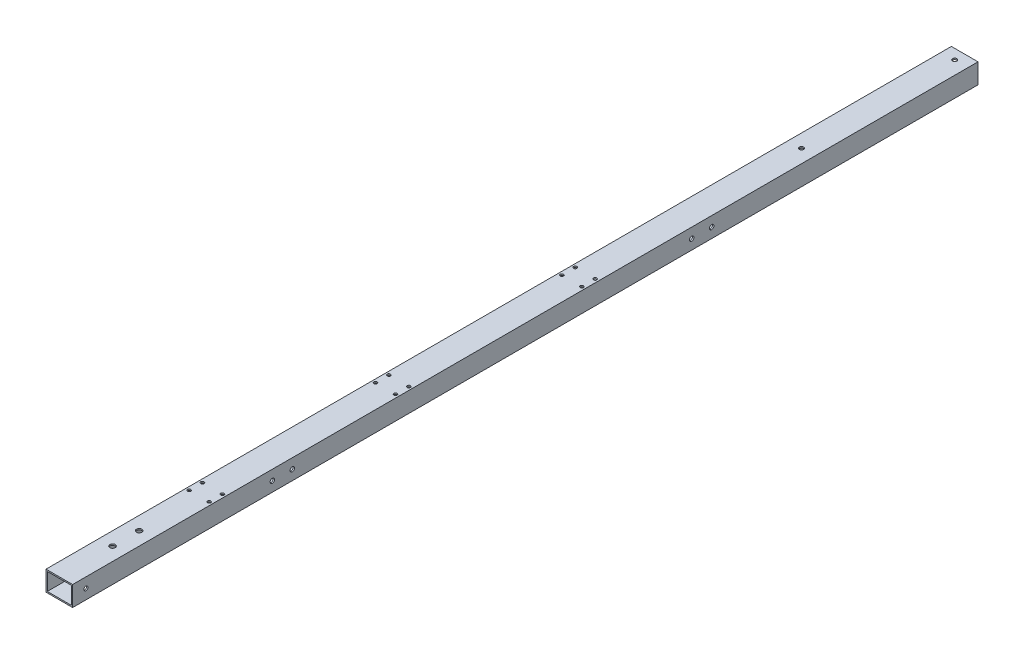
SolidWorks part; units mm, degrees
material "1060 合金"
ref_plane "前视基准面" through (0, 0, 0) normal (0, 0, 1) x (1, 0, 0)
ref_plane "上视基准面" through (0, 0, 0) normal (0, 1, 0) x (1, 0, 0)
ref_plane "右视基准面" through (0, 0, 0) normal (1, 0, 0) x (0, 0, -1)
other "Configuration Table"
sketch "草图1" plane through (0, 0, 0) normal (0, 0, 1) x (1, 0, 0)
  line L1 (0, 0) -> (20, 0)
  line L2 (0, 0) -> (0, -15)
  line L3 (0, -15) -> (20, -15)
  line L4 (20, 0) -> (20, -15)
  dimension "D1" = 15
  dimension "D2" = 20
extrude "拉伸-薄壁1" add sketch "草图1" along normal blind 800 thin thin type one direction reverse wall 1
sketch "草图2" plane through (0, -15, 0) normal (0, -1, 0) x (1, 0, 0)
  circle A1 centre (7.5, 825) radius 2.6
  circle A2 centre (7.5, 825) radius 2.6
  dimension "D1" = 0
extrude "切除-拉伸1" [suppressed] cut sketch "草图2" against normal up to next
sketch "草图3" plane through (0, 0, 0) normal (-1, 0, 0) x (0, 0, 1)
  line L0 (800, 0) -> (0, 0) construction
  line L1 (0, 0) -> (0, -15) construction
  circle A0 centre (215, -7.5) radius 1.7
  circle A1 centre (170, -7.5) radius 1.7
  dimension "D1" = 3.4
  dimension "D2" = 3.4
  dimension "D3" = 45
  dimension "D4" = 7.5
  dimension "D5" = 7.5
  dimension "D6" = 170
sketch "草图4" plane through (20, 0, 0) normal (1, 0, 0) x (0, 0, -1)
  line L0 (-800, -15) -> (0, -15) construction
  line L1 (-800, -15) -> (-800, 0) construction
  circle A0 centre (-790, -7.5) radius 1.5
  dimension "D1" = 3
  dimension "D2" = 7.5
  dimension "D3" = 10
extrude "切除-拉伸3" cut sketch "草图4" against normal through all
sketch "草图5" plane through (20, 0, 0) normal (1, 0, 0) x (0, 0, -1)
  line L0 (-800, 0) -> (0, 0) construction
  line L1 (0, -15) -> (0, 0) construction
  line L2 (-800, -1) -> (-800, -14) construction
  circle A0 centre (-320, -7.5) radius 1.65
  circle A1 centre (-335, -7.5) radius 1.65
  circle A2 centre (-635, -7.5) radius 1.65
  circle A3 centre (-650, -7.5) radius 1.65
  dimension "D1" = 3.3
  dimension "D4" = 3.3
  dimension "D7" = 7.5
  dimension "D9" = 3.3
  dimension "D10" = 3.3
  dimension "D2" = 7.5
  dimension "D3" = 15
  dimension "D5" = 7.5
  dimension "D6" = 320
  dimension "D8" = 7.5
  dimension "D11" = 15
  dimension "D12" = 150
extrude "切除-拉伸4" cut sketch "草图5" against normal through all
sketch "草图6" plane through (0, 0, 0) normal (0, 0, -1) x (-1, 0, 0)
  line L4 (0, -15) -> (0, 0)
  line L5 (0, 0) -> (-20, 0)
  line L6 (-20, 0) -> (-20, -15)
  line L7 (-20, -15) -> (0, -15)
  line L8 (0, -15) -> (0, 0)
  line L9 (0, 0) -> (-20, 0)
  line L10 (-20, 0) -> (-20, -15)
  line L11 (-20, -15) -> (0, -15)
  dimension "D1" = 0
extrude "切除-拉伸5" cut sketch "草图6" against normal blind 300
sketch "草图7" plane through (0, 0, 0) normal (0, 1, 0) x (1, 0, 0)
  line L0 (10, -300) -> (10, -861.2957) construction
  line L1 (0, -300) -> (20, -300) construction
  line L2 (0, -550) -> (263.5539, -550) construction
  line L3 (0, -800) -> (0, -300) construction
  circle A0 centre (2.5, -545) radius 1.25
  circle A1 centre (17.5, -545) radius 1.25
  circle A2 centre (17.5, -555) radius 1.25
  circle A3 centre (2.5, -555) radius 1.25
  circle A4 centre (2.5, -405) radius 1.25
  circle A5 centre (17.5, -405) radius 1.25
  circle A6 centre (17.5, -415) radius 1.25
  circle A7 centre (2.5, -415) radius 1.25
  circle A8 centre (2.5, -685) radius 1.25
  circle A9 centre (17.5, -685) radius 1.25
  circle A10 centre (17.5, -695) radius 1.25
  circle A11 centre (2.5, -695) radius 1.25
  circle A12 centre (2.5, -545) radius 1.25
  circle A13 centre (17.5, -545) radius 1.25
  circle A14 centre (17.5, -555) radius 1.25
  circle A15 centre (2.5, -555) radius 1.25
  line M12 (0, -300) -> (0, -800)
  line M14 (20, -800) -> (20, -300)
  dimension "D1" = 2.5
  dimension "D3" = 15
  dimension "D4" = 10
  dimension "D2" = 250
  dimension "D6" = 135
  dimension "D5" = 2
extrude "切除-拉伸6" cut sketch "草图7" against normal blind 155 contours A4 M12 | A7 M12 | A5 M14 | A6 M14 | A1 M14 | A0 M12 | A2 M14 | A8 M12 | A11 M12 | A9 M14 | A10 M14 | A3 region at (2.5, 0, 545) region at (17.5, 0, 545) region at (17.5, 0, 555) region at (2.5, 0, 405) region at (17.5, 0, 405) region at (17.5, 0, 415) region at (2.5, 0, 415) region at (2.5, 0, 685) region at (17.5, 0, 685) region at (17.5, 0, 695) region at (2.5, 0, 695)
sketch "草图8" plane through (0, 0, 300) normal (0, 0, -1) x (-1, 0, 0)
  line L0 (-1, -14) -> (-1, -1) construction
  line L1 (-1, -1) -> (-19, -1) construction
  line L2 (-19, -1) -> (-19, -14) construction
  line L3 (-19, -14) -> (-1, -14) construction
  line L4 (-20, -15) -> (0, -15)
  line L5 (0, -15) -> (0, 0)
  line L6 (0, 0) -> (-20, 0)
  line L7 (-20, 0) -> (-20, -15)
  line L8 (-20, -15) -> (0, -15)
  line L9 (0, -15) -> (0, 0)
  line L10 (0, 0) -> (-20, 0)
  line L11 (-20, 0) -> (-20, -15)
  line L12 (-1, -14) -> (-1, -1)
  line L13 (-1, -1) -> (-19, -1)
  line L14 (-19, -1) -> (-19, -14)
  line L15 (-19, -14) -> (-1, -14)
  dimension "D1" = 0
extrude "凸台-拉伸1" add sketch "草图8" along normal blind 180
sketch "草图9" plane through (0, 0, 0) normal (0, 1, 0) x (1, 0, 0)
  line L0 (0, -800) -> (0, -120) construction
  line L1 (20, -800) -> (0, -800) construction
  circle A0 centre (10, -740) radius 2.05
  circle A1 centre (10, -760) radius 2.05
  dimension "D1" = 4.1
  dimension "D2" = 10
  dimension "D3" = 60
  dimension "D4" = 2
extrude "切除-拉伸7" cut sketch "草图9" against normal blind 10
sketch "草图10" plane through (0, -15, 0) normal (0, -1, 0) x (1, 0, 0)
  line L0 (10, 765) -> (10, 785) construction
  line L1 (6, 765) -> (6, 785)
  line L2 (14, 765) -> (14, 785)
  line L3 (0, 800) -> (0, 120) construction
  line L4 (0, 800) -> (20, 800) construction
  arc A0 (6, 765) -> (14, 765) centre (10, 765) ccw
  arc A1 (14, 785) -> (6, 785) centre (10, 785) ccw
  point P2 (10, 775)
  dimension "D3" = 4
  dimension "D1" = 20
  dimension "D2" = 10
  dimension "D4" = 15
extrude "切除-拉伸8" cut sketch "草图10" against normal blind 10
sketch "草图11" plane through (0, -15, 0) normal (0, -1, 0) x (1, 0, 0)
  line L0 (0, 800) -> (0, 120) construction
  line L1 (20, 120) -> (0, 120) construction
  circle A0 centre (10, 127.5) radius 1.6
  circle A1 centre (10, 242.5) radius 1.6
  dimension "D1" = 3.2
  dimension "D2" = 10
  dimension "D3" = 7.5
  dimension "D4" = 2
extrude "切除-拉伸9" cut sketch "草图11" against normal through all
sketch "草图12" plane through (0, -15, 0) normal (0, -1, 0) x (1, 0, 0)
  line L0 (10, 248) -> (10, 238) construction
  line L1 (15, 248) -> (15, 238)
  line L2 (5, 248) -> (5, 238)
  line L3 (20, 120) -> (0, 120) construction
  line L4 (20, 800) -> (20, 120) construction
  arc A0 (15, 248) -> (5, 248) centre (10, 248) ccw
  arc A1 (5, 238) -> (15, 238) centre (10, 238) ccw
  point P2 (10, 243)
  dimension "D1" = 5
  dimension "D2" = 118
  dimension "D3" = 10
  dimension "D4" = 10
extrude "切除-拉伸10" cut sketch "草图12" against normal up to next
